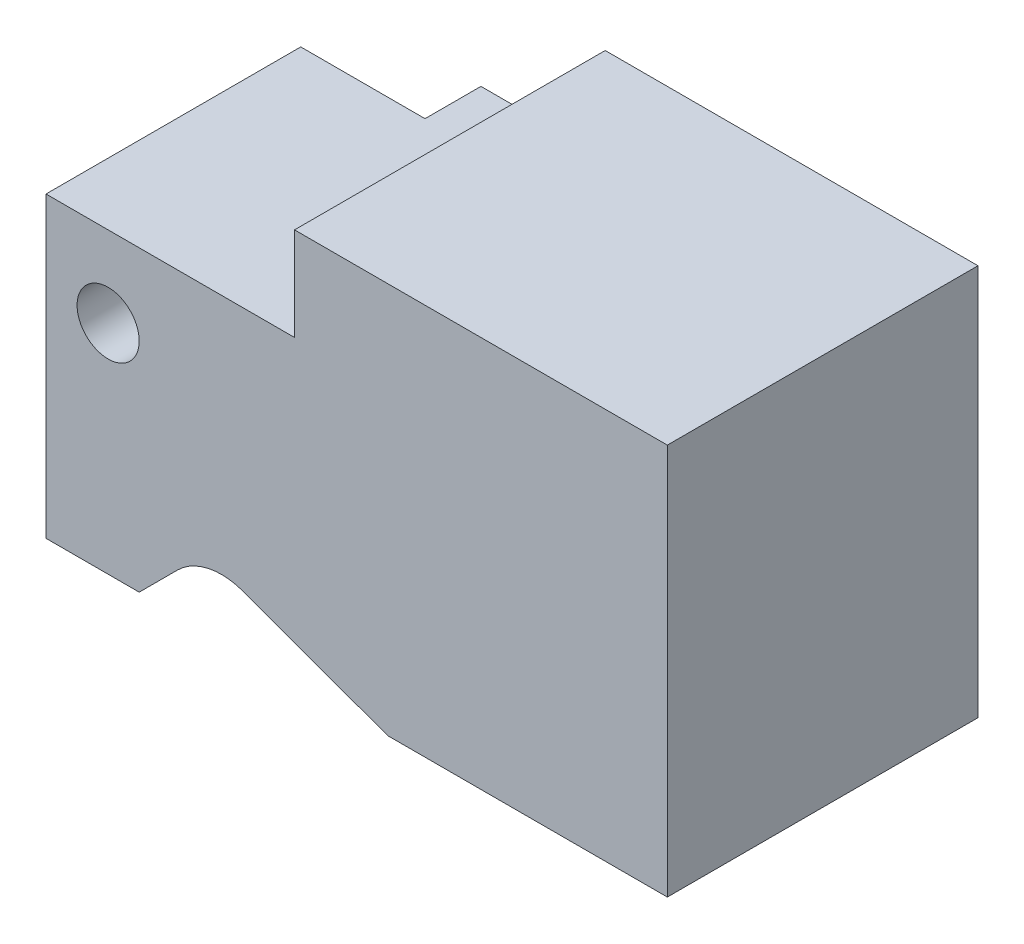
SolidWorks part; units mm, degrees
ref_plane "前基準面" through (0, 0, 0) normal (0, 0, 1) x (1, 0, 0)
ref_plane "上基準面" through (0, 0, 0) normal (0, 1, 0) x (1, 0, 0)
ref_plane "右基準面" through (0, 0, 0) normal (1, 0, 0) x (0, 0, -1)
sketch "草圖1" plane through (0, 0, 0) normal (0, 0, 1) x (1, 0, 0)
  line L1 (0, 0) -> (100, 0)
  line L2 (0, 0) -> (0, 63)
  line L3 (0, 63) -> (100, 63)
  line L4 (100, 0) -> (100, 63)
  dimension "D1" = 100
  dimension "D2" = 63
extrude "填料-伸長1" add sketch "草圖1" along normal blind 50
sketch "草圖2" plane through (0, 0, 0) normal (0, 0, -1) x (-1, 0, 0)
  line L0 (-40, 63) -> (-40, 48)
  line L1 (-100, 63) -> (0, 63) construction
  line L2 (-40, 48) -> (0, 48)
  line L3 (0, 63) -> (0, 0) construction
  line L4 (-40, 63) -> (0, 63)
  line L5 (0, 63) -> (0, 48)
  dimension "D1" = 15
  dimension "D2" = 40
extrude "除料-伸長2" cut sketch "草圖2" against normal through all
sketch "草圖3" plane through (0, 0, 0) normal (0, 0, -1) x (-1, 0, 0)
  line L1 (0, 0) -> (-100, 0) construction
  line L4 (0, 48) -> (0, 0) construction
  line L5 (-20, 35) -> (-20, 48)
  circle A0 centre (-10, 35) radius 5
  arc A1 (0, 15) -> (-20, 35) centre (0, 35) cw
  line M4 (0, 48) -> (-40, 48)
  line M9 (0, 0) -> (0, 48)
  dimension "D3" = 10
  dimension "D4" = 20
  dimension "D5" = 35
  dimension "D2" = 10
  dimension "D1" = 10
extrude "除料-伸長3" cut sketch "草圖3" against normal blind 9 contours A1 L5 A0 M9 M4 | A0 region at (19.6141, 41.5, 0) region at (10, 35, 0)
extrude "除料-伸長4" cut sketch "草圖3<3>" against normal through all contours A0
sketch "草圖3<3>" plane through (0, 0, 0) normal (0, 0, -1) x (-1, 0, 0) same geometry as "草圖3"
sketch "草圖6" plane through (0, 0, 0) normal (0, 0, -1) x (-1, 0, 0)
  line L0 (-15, 0) -> (-21.1691, 6.1691)
  line L1 (0, 0) -> (-100, 0) construction
  line L2 (0, 15) -> (0, 0) construction
  line L3 (-31.6603, 8.4949) -> (-55, 0)
  line L4 (-55, 0) -> (-15, 0)
  arc A0 (-21.1691, 6.1691) -> (-31.6603, 8.4949) centre (-28.2401, -0.902) ccw
  dimension "D2" = 10
  dimension "D1" = 45
  dimension "D3" = 15
  dimension "D4" = 20
  dimension "D5" = 40
extrude "除料-伸長5" cut sketch "草圖6" against normal through all
sketch "草圖7" plane through (0, 0, 0) normal (0, 0, -1) x (-1, 0, 0)
  line L0 (-55, 0) -> (-100, 0) construction
  line L1 (-100, 0) -> (-100, 63) construction
  line L2 (-70, 45) -> (-70, 40)
  line L3 (-70, 30) -> (-70, 25)
  line L4 (-70, 78.4299) -> (-70, 45)
  line L5 (-70, 25) -> (-70, 10)
  circle A0 centre (-70, 35) radius 5
  circle A1 centre (-70, 35) radius 25
  arc A2 (-70, 45) -> (-70, 25) centre (-70, 35) cw
  point P7 (-70, 78.4299)
  point P17 (-95.3767, 18.2724)
  dimension "D1" = 10
  dimension "D4" = 50
  dimension "D5" = 10
  dimension "D2" = 35
  dimension "D3" = 30
extrude "除料-伸長6" cut sketch "草圖7" against normal blind 13 contours A1
extrude "填料-伸長2" add sketch "草圖7<3>" along normal blind 5 separate body contours A2 L2 A0 L3 region at (60.2236, 35, 0)
sketch "草圖7<3>" plane through (0, 0, 0) normal (0, 0, -1) x (-1, 0, 0) same geometry as "草圖7"
extrude "填料-伸長3" add sketch "草圖7<4>" along normal blind 8 contours A0 region at (70, 35, 0)
sketch "草圖7<4>" plane through (0, 0, 0) normal (0, 0, -1) x (-1, 0, 0) same geometry as "草圖7"
sketch "草圖8" plane through (0, 0, 0) normal (0, 0, -1) x (-1, 0, 0)
  line L0 (-70, 63) -> (-70, 60)
  line L1 (-100, 63) -> (-40, 63) construction
  circle A0 centre (-70, 35) radius 25 construction
  circle A1 centre (-128.077, 61.5) radius 25
  point P9 (0, 0)
  point P10 (0, 0)
  point P11 (0, 0)
  dimension "D1" = 50
